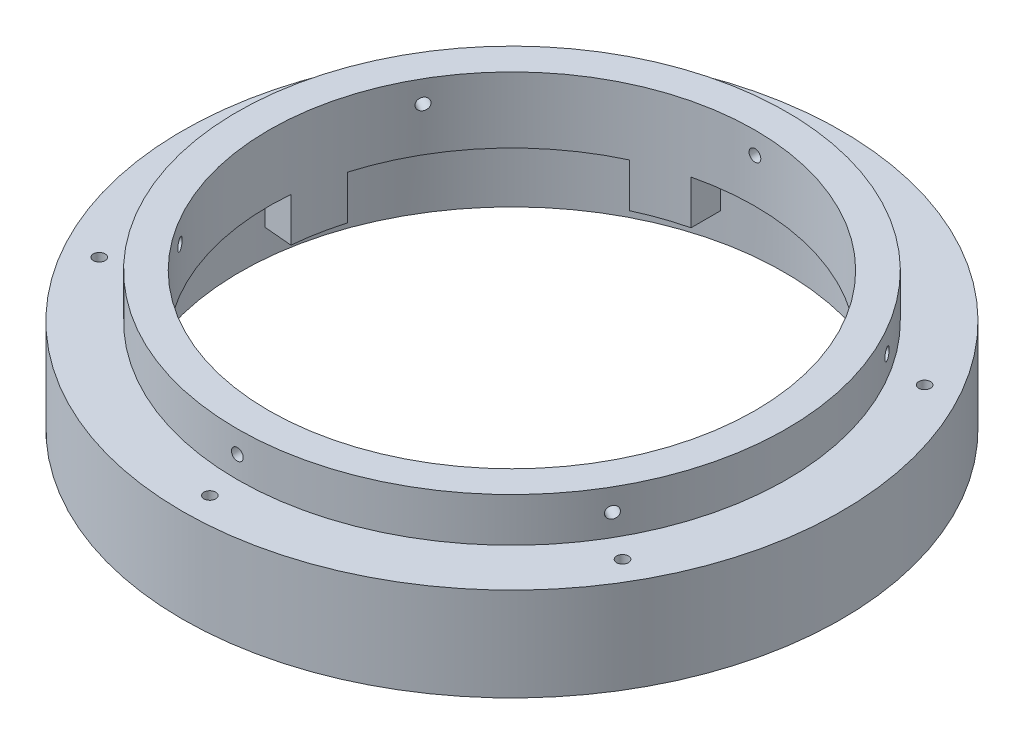
SolidWorks part; units mm, degrees
ref_plane "Front Plane" through (0, 0, 0) normal (0, 0, 1) x (1, 0, 0)
ref_plane "Top Plane" through (0, 0, 0) normal (0, 1, 0) x (1, 0, 0)
ref_plane "Right Plane" through (0, 0, 0) normal (1, 0, 0) x (0, 0, -1)
sketch "Sketch1" plane through (0, 0, 0) normal (0, 1, 0) x (1, 0, 0)
  circle A0 centre (0, 0) radius 63.5
  circle A1 centre (0, 0) radius 76.2
  circle A2 centre (0, 0) radius 56.1975
  circle A4 centre (0, 0) radius 62.865
  dimension "D1" = 152.4
  dimension "D3" = 112.395
  dimension "D2" = 12.7
  dimension "D4" = 13.335
extrude "Boss-Extrude1" add sketch "Sketch1" along normal blind 15.24 contours A0 A2 | A0 A4 region at (-63.3204, 0, 0) region at (-61.0869, 0, 0)
extrude "Boss-Extrude2" add sketch "Sketch1<4>" along normal blind 5.08 and the other way blind 16.51 contours A1 A0 | A0 A4 region at (-63.3204, 0, 0) region at (-74.0447, 0, 0)
sketch "Sketch1<4>" plane through (0, 0, 0) normal (0, 1, 0) x (1, 0, 0) same geometry as "Sketch1"
sketch "Sketch3" plane through (0, -16.51, 0) normal (0, -1, 0) x (1, 0, 0)
  line L0 (0, 0) -> (-68.319, 5.9771) construction
  line L1 (0, 0) -> (0, 69.85) construction
  line L2 (0, 0) -> (48.9804, 58.3726)
  line L3 (0, 0) -> (13.232, 75.0424)
  line L4 (-13.2113, -54.6225) -> (-13.2113, -60.147)
  line L5 (13.2113, -54.6225) -> (13.2113, -60.147)
  line L6 (-13.2113, -60.147) -> (13.2113, -60.147)
  line L7 (-13.2113, -60.147) -> (-13.2113, -61.4611)
  line L8 (-23.7501, -50.9322) -> (-26.5679, -56.975)
  line L9 (0, 0) -> (-23.7501, -50.9322) construction
  circle A0 centre (-68.319, 5.9771) radius 4.8895
  circle A1 centre (0, 69.85) radius 1.3589
  circle A2 centre (0, 0) radius 76.2 construction
  circle A5 centre (0, 0) radius 56.1975 construction
  arc A7 (-26.5679, -56.975) -> (-13.2113, -61.4611) centre (0, 0) ccw
  arc A9 (-23.7501, -50.9322) -> (-13.2113, -54.6225) centre (0, 0) ccw
  circle A12 centre (0, 0) radius 62.865 construction
  point P0 (0, -60.147)
  point P13 (0, 0)
  point P16 (-26.5679, -56.975)
  point P17 (0, 0)
  point P22 (0, 0)
  point P24 (-26.8363, -57.5505)
  point P27 (-26.8363, -57.5505)
  point P28 (0, 0)
  point P29 (-26.8363, -57.5505)
  point P30 (-13.2113, -61.4611)
  point P31 (-26.5679, -56.975)
  point P33 (0, 0)
  point P34 (0, 0)
  point P35 (0, 0)
  point P37 (0, 0)
  point P38 (-13.2113, -61.4611)
  dimension "D4" = 9.779
  dimension "D5" = 2.7178
  dimension "D2" = 85
  dimension "D3" = 69.85
  dimension "D6" = 30
  dimension "D7" = 10
  dimension "D9" = 26.4227
  dimension "D8" = 5.5245
  dimension "D10" = 25
extrude "Cut-Extrude1" cut sketch "Sketch3" against normal blind 15.24 contours A0 region at (-68.319, -16.51, 5.9771)
extrude "Cut-Extrude2" cut sketch "Sketch3<3>" against normal through all contours A1 region at (0, -16.51, 69.85)
sketch "Sketch3<3>" plane through (0, -16.51, 0) normal (0, -1, 0) x (1, 0, 0) same geometry as "Sketch3"
pattern_circular "CirPattern1" count 3 over 360 about axis through (0, -16.51, 0) along (0, 1, 0) of "Cut-Extrude1"
pattern_circular "CirPattern2" count 6 over 360 about axis through (0, -16.51, 0) along (0, 1, 0) of "Cut-Extrude2"
ref_plane "Plane1" through (0, 0, 76.2) normal (0, 0, 1) x (1, 0, 0)
sketch "Sketch5" plane through (0, 0, 76.2) normal (0, 0, 1) x (1, 0, 0)
  line L0 (0, -16.51) -> (0, 10.16) construction
  line L1 (-1.3589, -16.51) -> (1.3589, -16.51) construction
  circle A0 centre (0, 10.16) radius 1.3589
  dimension "D2" = 2.7178
  dimension "D1" = 26.67
extrude "Cut-Extrude3" cut sketch "Sketch5" against normal up to surface (132.3811 mm away) up to face at (0, 15.24, 56.1975)
extrude "Boss-Extrude3" add sketch "Sketch3<11>" along normal blind 10.16 from surface contours L4 A9 L8 A7 L7 starting at face at (0, 0, 56.1975)
sketch "Sketch3<11>" plane through (0, -16.51, 0) normal (0, -1, 0) x (1, 0, 0) same geometry as "Sketch3"
pattern_circular "CirPattern3" count 6 over 360 about axis through (0, 15.24, 0) along (0, 1, 0) of "Cut-Extrude3", "Boss-Extrude3"
equation "\"Middle Coupler Inner Daimeter\"= 3.875in"
equation "\"Middle Coupler  Wall Thickness\" = 0.25in"
equation "\"Middle Coupler Bottom Thickness\"= 0.2in"
equation "\"Bearing Rail Offset\"= 0.45in"
equation "\"3-56 UNF Tap\"= 0.089in"
equation "\"3-48 Tap\"= 0.079in"
equation "\"3-56 UNF Clearance\"= 0.104in"
equation "\"3-48 Clearance\" = 0.104in"
equation "\"Ball Bearing Distance\"= 0.03in"
equation "\"TCA Outer Diameter\" = 6in"
equation "\"Interstage Aeroframe Wall Thickness\" = 0.072in"
equation "\"Compression Spring OD\"= 0.42in"
equation "\"10-24 Tap\"= 0.157in"
equation "\"10-24 Clearance\"= 0.196in"
equation "\"Lower Stage Fuselage Wall Thickness\" = 0.25in"
equation "\"6-32 Tap\" = 0.107in"
equation "\"6-32 Clearance\" = 0.144"
equation "\"1/4-20 Tap\" = 0.201in"
equation "\"12-24 Tap\" = 0.177in"
equation "\"D1@Sketch1\"=\"TCA Outer Diameter\""
equation "\"D5@Sketch3\"=\"6-32 Tap\""
equation "\"D1@Sketch5\"=\"D2@Boss-Extrude2\"+(\"D1@Boss-Extrude2\"+\"D1@Boss-Extrude1\")/2"
equation "\"D2@Sketch5\"=\"6-32 Tap\""
equation "\"D8@Sketch3\"=3/16+0.03"
equation "\"D3@Sketch1\"=\"Middle Coupler Inner Daimeter\" + 0.55"
equation "\"D4@Sketch3\"=0.375 + 0.01"
